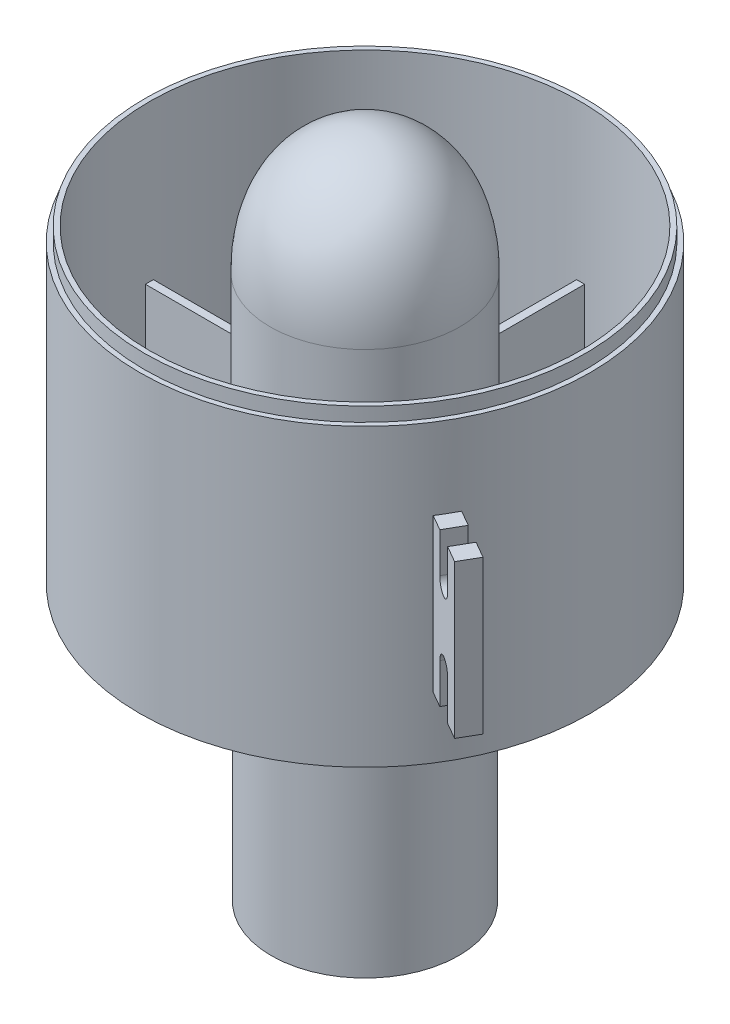
SolidWorks part; units mm, degrees
ref_plane "Front Plane" through (0, 0, 0) normal (0, 0, 1) x (1, 0, 0)
ref_plane "Top Plane" through (0, 0, 0) normal (0, 1, 0) x (1, 0, 0)
ref_plane "Right Plane" through (0, 0, 0) normal (1, 0, 0) x (0, 0, -1)
sketch "Sketch1" plane through (0, 0, 0) normal (0, 1, 0) x (1, 0, 0)
  circle A0 centre (0, 0) radius 36.8
  circle A2 centre (0, 0) radius 35.2
  dimension "D1" = 73.6
  dimension "D2" = 1.6
extrude "Boss-Extrude1" add sketch "Sketch1" along normal blind 50.5
sketch "Sketch2" plane through (0, 0, 0) normal (0, -1, 0) x (1, 0, 0)
  line L0 (-36.8, 0) -> (-16, 0) construction
  line L1 (15.9868, 0.65) -> (35.194, 0.65)
  line L2 (15.9868, -0.65) -> (35.194, -0.65)
  line L3 (11.764, -10.8447) -> (25.3455, -24.4263)
  line L4 (10.8447, -11.764) -> (24.4263, -25.3455)
  line L5 (0.65, -15.9868) -> (0.65, -35.194)
  line L6 (-0.65, -15.9868) -> (-0.65, -35.194)
  line L7 (-10.8447, -11.764) -> (-24.4263, -25.3455)
  line L8 (-11.764, -10.8447) -> (-25.3455, -24.4263)
  line L9 (-15.9868, -0.65) -> (-35.194, -0.65)
  line L10 (-15.9868, 0.65) -> (-35.194, 0.65)
  line L11 (-11.764, 10.8447) -> (-25.3455, 24.4263)
  line L12 (-10.8447, 11.764) -> (-24.4263, 25.3455)
  line L13 (-0.65, 15.9868) -> (-0.65, 35.194)
  line L14 (0.65, 15.9868) -> (0.65, 35.194)
  line L15 (10.8447, 11.764) -> (24.4263, 25.3455)
  line L16 (11.764, 10.8447) -> (25.3455, 24.4263)
  line L17 (-15, 0) -> (15.7396, 0) construction
  circle A0 centre (0, 0) radius 36.8 construction
  arc A1 (-15.9868, -0.65) -> (-11.764, -10.8447) centre (0, 0) ccw
  circle A2 centre (0, 0) radius 15
  circle A3 centre (0, 0) radius 35.2 construction
  circle A4 centre (0, 0) radius 16 construction
  arc A5 (-11.764, 10.8447) -> (-15.9868, 0.65) centre (0, 0) ccw
  arc A6 (-0.65, 15.9868) -> (-10.8447, 11.764) centre (0, 0) ccw
  arc A7 (10.8447, 11.764) -> (0.65, 15.9868) centre (0, 0) ccw
  arc A8 (15.9868, 0.65) -> (11.764, 10.8447) centre (0, 0) ccw
  arc A9 (11.764, -10.8447) -> (15.9868, -0.65) centre (0, 0) ccw
  arc A10 (0.65, -15.9868) -> (10.8447, -11.764) centre (0, 0) ccw
  arc A11 (-10.8447, -11.764) -> (-0.65, -15.9868) centre (0, 0) ccw
  arc A12 (-35.194, 0.65) -> (-35.194, -0.65) centre (0, 0) ccw
  arc A13 (-24.4263, 25.3455) -> (-25.3455, 24.4263) centre (0, 0) ccw
  arc A14 (0.65, 35.194) -> (-0.65, 35.194) centre (0, 0) ccw
  arc A15 (25.3455, 24.4263) -> (24.4263, 25.3455) centre (0, 0) ccw
  arc A16 (35.194, -0.65) -> (35.194, 0.65) centre (0, 0) ccw
  arc A17 (24.4263, -25.3455) -> (25.3455, -24.4263) centre (0, 0) ccw
  arc A18 (-0.65, -35.194) -> (0.65, -35.194) centre (0, 0) ccw
  arc A19 (-25.3455, -24.4263) -> (-24.4263, -25.3455) centre (0, 0) ccw
  point P46 (0, 0)
  dimension "D1" = 32
  dimension "D3" = 1.3
  dimension "D2" = 1
  dimension "D4" = 8
extrude "Boss-Extrude2" add sketch "Sketch2" against normal blind 25
ref_axis "Axis1" through (0, 25, 0) along (0, -1, 0)
ref_plane "Plane1" through (0, 0, 0) normal (-0.5, 0, 0.866) x (0, -1, 0)
sketch "Sketch3" plane through (0, 0, 0) normal (-0.5, 0, 0.866) x (0, -1, 0)
  line L0 (0, 36.8008) -> (-50.5, 36.8008) construction
  line L1 (0, -36.8) -> (0, 36.8) construction
  line L2 (-50.5, 36.8) -> (-50.5, -36.8) construction
  line L3 (-35, 41.45) -> (-10, 41.45) construction
  line L4 (-35, 36.8008) -> (-10, 36.8008)
  line L5 (-35, 36.8008) -> (-35, 39.7)
  line L6 (-35, 46.3008) -> (-10, 46.3008)
  line L7 (-10, 36.8008) -> (-10, 39.7)
  line L8 (-28.5, 43.2) -> (-35, 43.2)
  line L9 (-28.5, 39.7) -> (-35, 39.7)
  line L10 (-35, 43.2) -> (-35, 46.3008)
  line L11 (-22.5, 46.3008) -> (-22.5, 36.8008) construction
  line L12 (-16.5, 39.7) -> (-10, 39.7)
  line L13 (-16.5, 43.2) -> (-10, 43.2)
  line L14 (-10, 43.2) -> (-10, 46.3008)
  line L15 (-50.5, 0) -> (0, 0) construction
  line L16 (-16.5, -39.7) -> (-10, -39.7)
  line L17 (-16.5, -43.2) -> (-10, -43.2)
  line L18 (-35, -43.2) -> (-35, -46.3008)
  line L19 (-28.5, -43.2) -> (-35, -43.2)
  line L20 (-28.5, -39.7) -> (-35, -39.7)
  line L21 (-35, -36.8008) -> (-35, -39.7)
  line L22 (-35, -36.8008) -> (-10, -36.8008)
  line L23 (-10, -36.8008) -> (-10, -39.7)
  line L24 (-10, -43.2) -> (-10, -46.3008)
  line L25 (-35, -46.3008) -> (-10, -46.3008)
  arc A0 (-28.5, 39.7) -> (-28.5, 43.2) centre (-28.5, 41.45) ccw
  arc A1 (-16.5, 39.7) -> (-16.5, 43.2) centre (-16.5, 41.45) cw
  arc A2 (-28.5, -39.7) -> (-28.5, -43.2) centre (-28.5, -41.45) cw
  arc A3 (-16.5, -39.7) -> (-16.5, -43.2) centre (-16.5, -41.45) ccw
  point P41 (0, 36.8093)
  point P42 (-48, 36.8008)
  dimension "D4" = 3.5
  dimension "D1" = 10
  dimension "D2" = 25
  dimension "D3" = 9.5
  dimension "D5" = 6.5
extrude "Boss-Extrude3" add sketch "Sketch3" along normal blind 1.7 and the other way blind 1.7 separate body
sketch "Sketch4" plane through (31.8704, 0, 18.4004) normal (-0.866, 0, -0.5) x (-0.5, 0, 0.866)
  line L1 (-1.7, 35) -> (1.7, 35)
  line L2 (-1.7, 35) -> (-1.7, 10)
  line L3 (-1.7, 10) -> (1.7, 10)
  line L4 (1.7, 35) -> (1.7, 10)
extrude "Boss-Extrude4" add sketch "Sketch4" along normal up to surface (0.0401 mm away) up to face at (0, 50.5, 36.8)
sketch "Sketch5" plane through (0, 50.5, 0) normal (0, 1, 0) x (1, 0, 0)
  circle A0 centre (0, 0) radius 36.8 construction
  circle A1 centre (0, 0) radius 36.8
  circle A2 centre (0, 0) radius 36
  dimension "D1" = 0.8
extrude "Cut-Extrude1" cut sketch "Sketch5" against normal blind 2.3
sketch "Sketch6" plane through (0, 0, 0) normal (0, -1, 0) x (1, 0, 0)
  circle A0 centre (0, 0) radius 15.3
  dimension "D1" = 30.6
extrude "Boss-Extrude5" add sketch "Sketch6" along normal blind 50
chamfer "Chamfer1" distance 5 angle 60 1 edges at (0, -50, -15.3) first distance on face at (0, -50, -15.3)
sketch "Sketch7" plane through (0, 0, 0) normal (0, 1, 0) x (1, 0, 0)
  circle A0 centre (0, 0) radius 15.5
  dimension "D1" = 31
extrude "Boss-Extrude6" add sketch "Sketch7" along normal blind 44
sketch "Sketch8" plane through (0, 0, 0) normal (-0.5, 0, 0.866) x (0, -1, 0)
  line L0 (-44, 0) -> (-83.5149, 0) construction
  line L1 (-44, 15.5) -> (-44, -15.5) construction
  line L2 (-64, 19.8889) -> (-64, -13.7445) construction
  line L3 (-64, -8.4837) -> (-64, 8.4837) construction
  line L4 (-55.1765, 15.5) -> (-32.8235, 15.5) construction
  line L5 (-44, 15.5) -> (-44, 0)
  line L6 (-64, 0) -> (-44, 0)
  spline S0 degree 3 poles (-44, 15.5) (-57.9706, 15.5) (-64, 7.0697) (-64, 0) knots 0 0 0 0 1 1 1 1
  dimension "D1" = 20
revolve "Revolve2" add sketch "Sketch8" angle 360 about axis through (0, 25, 0) along (0, -1, 0)
